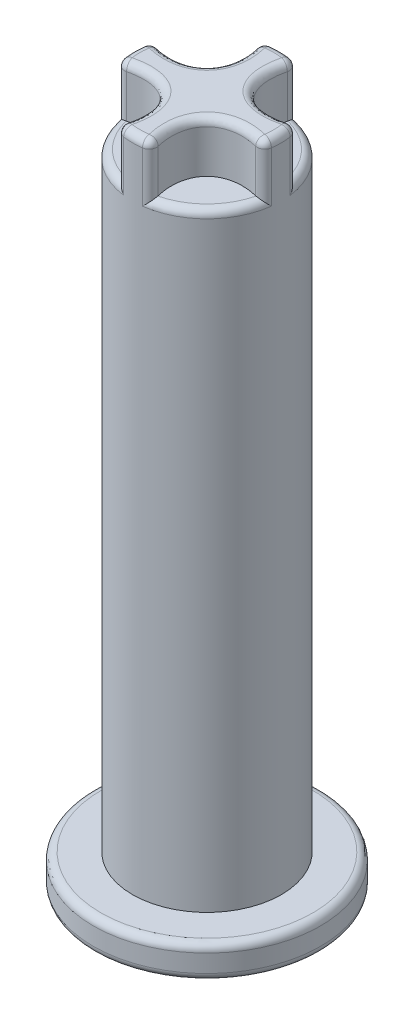
SolidWorks part; units mm, degrees
ref_plane "Front Plane" through (0, 0, 0) normal (0, 0, 1) x (1, 0, 0)
ref_plane "Top Plane" through (0, 0, 0) normal (0, 1, 0) x (1, 0, 0)
ref_plane "Right Plane" through (0, 0, 0) normal (1, 0, 0) x (0, 0, -1)
sketch "Sketch1" plane through (0, 0, 0) normal (0, 1, 0) x (1, 0, 0)
  circle A0 centre (0, 0) radius 2.95
extrude "Boss-Extrude1" add sketch "Sketch1" along normal blind 27.4
sketch "Sketch2" plane through (0, 0, 0) normal (0, 1, 0) x (1, 0, 0)
  circle A0 centre (0, 0) radius 4.5
extrude "Boss-Extrude2" add sketch "Sketch2" along normal blind 1.3
sketch "Sketch3" plane through (0, 27.4, 0) normal (0, 1, 0) x (1, 0, 0)
  ellipse E0 centre (-3.4, 3.4) end of major axis (-5.875, 5.875) minor radius 2
  ellipse E1 centre (3.4, 3.4) end of major axis (5.875, 5.875) minor radius 2
  ellipse E2 centre (3.4, -3.4) end of major axis (5.875, -5.875) minor radius 2
  ellipse E3 centre (-3.4, -3.4) end of major axis (-5.875, -5.875) minor radius 2
extrude "Cut-Extrude1" cut sketch "Sketch3" against normal blind 2
fillet "Fillet2" radius 0.3 22 edges at (-2.086, 25.4, -2.086) (2.086, 25.4, -2.086) (2.086, 25.4, 2.086) (-2.086, 25.4, 2.086) (-2.862, 26.4, -0.7152) (-0.7152, 26.4, -2.862) (0.7152, 26.4, -2.862) (2.862, 26.4, -0.7152) (2.862, 26.4, 0.7152) (0.7152, 26.4, 2.862) (-0.7152, 26.4, 2.862) (-2.862, 26.4, 0.7152) (2.95, 27.4, 0) (0, 27.4, -2.95) (-2.95, 27.4, 0) (0, 27.4, 2.95) (0.925, 27.4, 0.925) (0.925, 27.4, -0.925) (-0.925, 27.4, -0.925) (-0.925, 27.4, 0.925) (0, 0, 4.5) (0, 1.3, 4.5)
